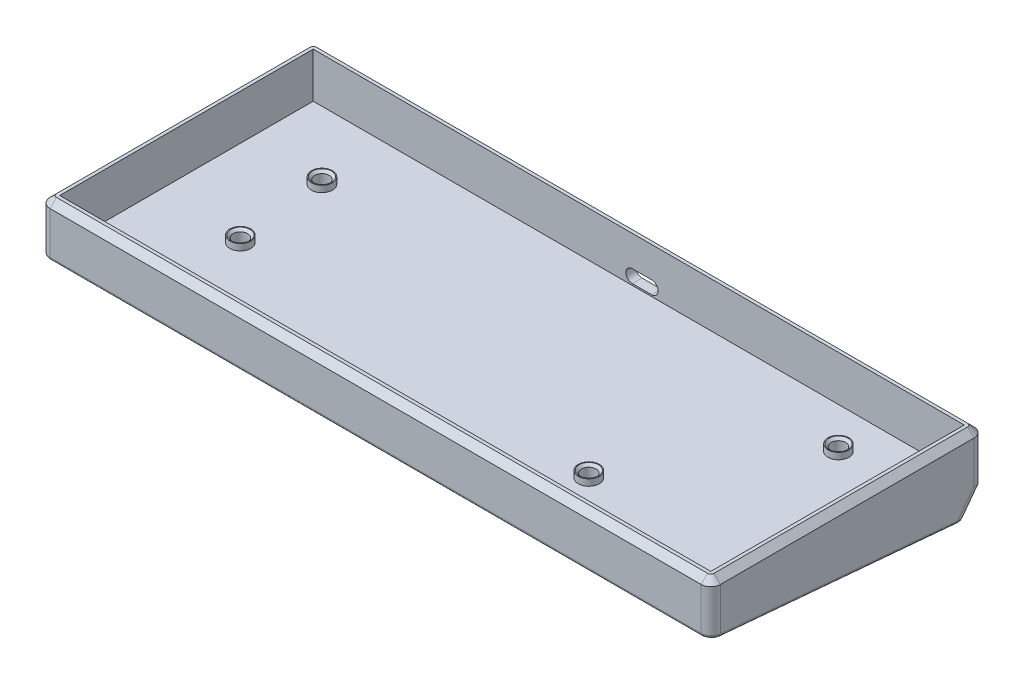
SolidWorks part; units mm, degrees
ref_plane "Front Plane" through (0, 0, 0) normal (0, 0, 1) x (1, 0, 0)
ref_plane "Top Plane" through (0, 0, 0) normal (0, 1, 0) x (1, 0, 0)
ref_plane "Right Plane" through (0, 0, 0) normal (1, 0, 0) x (0, 0, -1)
sketch "Sketch4" plane through (0, 0, 0) normal (0, 1, 0) x (1, 0, 0)
  line L0 (-2.525, 73.675) -> (197.5, 73.675)
  line L1 (-2.525, 73.675) -> (-2.525, -3)
  line L2 (197.5, 73.675) -> (197.5, -3)
  line L3 (-2.525, -3) -> (197.5, -3)
  line L42 (-6.525, 77.675) -> (201.5, 77.675)
  line L47 (201.5, 77.675) -> (201.5, -7)
  line L48 (-3.525, 74.675) -> (198.5, 74.675)
  line L49 (198.5, 74.675) -> (198.5, -4)
  line L50 (-3.525, -4) -> (198.5, -4)
  line L51 (-3.525, 74.675) -> (-3.525, -4)
  line L52 (-6.525, -7) -> (201.5, -7)
  line L53 (-6.525, 77.675) -> (-6.525, -7)
  line L54 (-2.525, 73.675) -> (197.5, 73.675)
  line L55 (197.5, 73.675) -> (197.5, -3)
  line L56 (197.5, -3) -> (-2.525, -3)
  line L57 (-2.525, -3) -> (-2.525, 73.675)
  circle A4 centre (23.1153, 25.4289) radius 1.5
  circle A5 centre (172.0218, 62.0916) radius 1.5
  circle A6 centre (20.1153, 53.7438) radius 1.5
  circle A7 centre (140.3993, 16.2494) radius 1.5
  dimension "D1" = 3
  dimension "D32" = 1
extrude "Boss-Extrude1" add sketch "Sketch4" along normal blind 2 contours L42 L53 L52 L47 L51 L48 L49 L50 | L50 L49 L48 L51 region at (97.4875, 0, -75.429)
sketch "Sketch9" plane through (0, 2, 0) normal (0, 1, 0) x (1, 0, 0)
  line L0 (-3.525, 74.675) -> (198.5, 74.675)
  line L1 (-6.525, 77.675) -> (201.5, 77.675)
  line L2 (-6.525, 77.675) -> (-6.525, -7)
  line L3 (-6.525, -7) -> (201.5, -7)
  line L4 (201.5, 77.675) -> (201.5, -7)
  line L5 (198.5, 74.675) -> (198.5, -4)
  line L6 (-3.525, -4) -> (198.5, -4)
  line L7 (-3.525, 74.675) -> (-3.525, -4)
  dimension "D1" = 3
extrude "Boss-Extrude2" add sketch "Sketch9" along normal blind 14
sketch "Sketch10" plane through (-6.525, 0, 0) normal (-1, 0, 0) x (0, 0, 1)
  line L0 (-77.675, 0) -> (-72.4404, -6.9501)
  line L1 (-72.4404, -6.9501) -> (7, 0)
  line L3 (-77.675, 0) -> (7, 0)
  dimension "D1" = 5
extrude "Boss-Extrude3" add sketch "Sketch10" against normal up to surface (208.025 mm away) up to face at (201.5, 8, -35.3375)
fillet "Fillet1" radius 3 6 edges at (201.5, 8, -77.675) (201.5, -3.4751, -75.0577) (201.5, 8, 7) (-6.525, -3.4751, -75.0577) (-6.525, 8, -77.675) (-6.525, 8, 7)
chamfer "Chamfer1" distance 2 angle 45 8 edges at (200.6213, 16, 6.1213) (97.4875, 16, 7) (-5.6463, 16, 6.1213) (-6.525, 16, -35.3375) (-5.6463, 16, -76.7963) (97.4875, 16, -77.675) (200.6213, 16, -76.7963) (201.5, 16, -35.3375)
fillet "Fillet2" radius 1 8 edges at (-5.6463, -6.8598, -71.4084) (-6.525, -3.4522, -32.4584) (-5.6463, -0.0769, 6.1213) (97.4875, 0, 7) (200.6213, -0.0769, 6.1213) (201.5, -3.4522, -32.4584) (200.6213, -6.8598, -71.4084) (97.4875, -6.9501, -72.4404)
sketch "Sketch11" plane through (0, 0, -77.675) normal (0, 0, -1) x (-1, 0, 0)
  line L0 (-101.485, 4.5) -> (-95.485, 4.5) construction
  line L1 (-101.485, 6.5) -> (-95.485, 6.5)
  line L2 (-101.485, 2.5) -> (-95.485, 2.5)
  line L3 (3.525, 0) -> (-198.5, 0) construction
  line L4 (-198.5, 14) -> (-198.5, 0) construction
  arc A0 (-101.485, 6.5) -> (-101.485, 2.5) centre (-101.485, 4.5) ccw
  arc A1 (-95.485, 2.5) -> (-95.485, 6.5) centre (-95.485, 4.5) ccw
  point P2 (-98.485, 4.5)
  point P11 (-103.485, 4.5)
  point P12 (-93.485, 4.5)
  dimension "D3" = 10
  dimension "D1" = 4.5
  dimension "D2" = 100.015
  dimension "D4" = 2
extrude "Cut-Extrude1" cut sketch "Sketch11" against normal blind 8
sketch "Sketch13" plane through (0, 2, 0) normal (0, 1, 0) x (1, 0, 0)
  line L0 (-2.525, 73.675) -> (197.5, 73.675)
  line L1 (-2.525, 73.675) -> (-2.525, -3)
  line L2 (197.5, 73.675) -> (197.5, -3)
  line L3 (-2.525, -3) -> (197.5, -3)
  line L54 (-2.525, 73.675) -> (197.5, 73.675)
  line L55 (197.5, 73.675) -> (197.5, -3)
  line L56 (197.5, -3) -> (-2.525, -3)
  line L57 (-2.525, -3) -> (-2.525, 73.675)
  circle A8 centre (140.3993, 16.2494) radius 2.25
  circle A9 centre (172.0219, 62.0916) radius 2.25
  circle A10 centre (20.1153, 53.7438) radius 2.25
  circle A11 centre (23.1153, 25.4289) radius 2.25
  circle A12 centre (140.3993, 16.2494) radius 3.25
  circle A13 centre (172.0219, 62.0916) radius 3.25
  circle A14 centre (20.1153, 53.7438) radius 3.25
  circle A15 centre (23.1153, 25.4289) radius 3.25
  dimension "D1" = 4.5
  dimension "D2" = 4.5
  dimension "D3" = 4.5
  dimension "D4" = 4.5
  dimension "D5" = 1
  dimension "D6" = 1
  dimension "D7" = 1
  dimension "D8" = 1
extrude "Boss-Extrude4" add sketch "Sketch13" along normal blind 2 contours A12 A8 | A13 A9 | A15 A11 | A14 A10 region at (137.2412, 2, -16.2494) region at (168.8638, 2, -62.0916) region at (16.9572, 2, -53.7438) region at (19.9572, 2, -25.4289)
sketch "Sketch14" plane through (0, 4, 0) normal (0, 1, 0) x (1, 0, 0)
  circle A1 centre (172.0219, 62.0916) radius 2.25
  circle A2 centre (140.3993, 16.2494) radius 2.25
  circle A4 centre (20.1153, 53.7438) radius 2.25
  circle A5 centre (23.1153, 25.4289) radius 2.25
  dimension "D1" = 4.5
  dimension "D2" = 4.5
extrude "Cut-Extrude2" cut sketch "Sketch14" against normal blind 4
chamfer "Chamfer2" distance 0.75 angle 45 4 edges at (23.1153, 4, -23.1789) (140.3993, 4, -13.9994) (172.0219, 4, -59.8416) (20.1153, 4, -51.4938)
